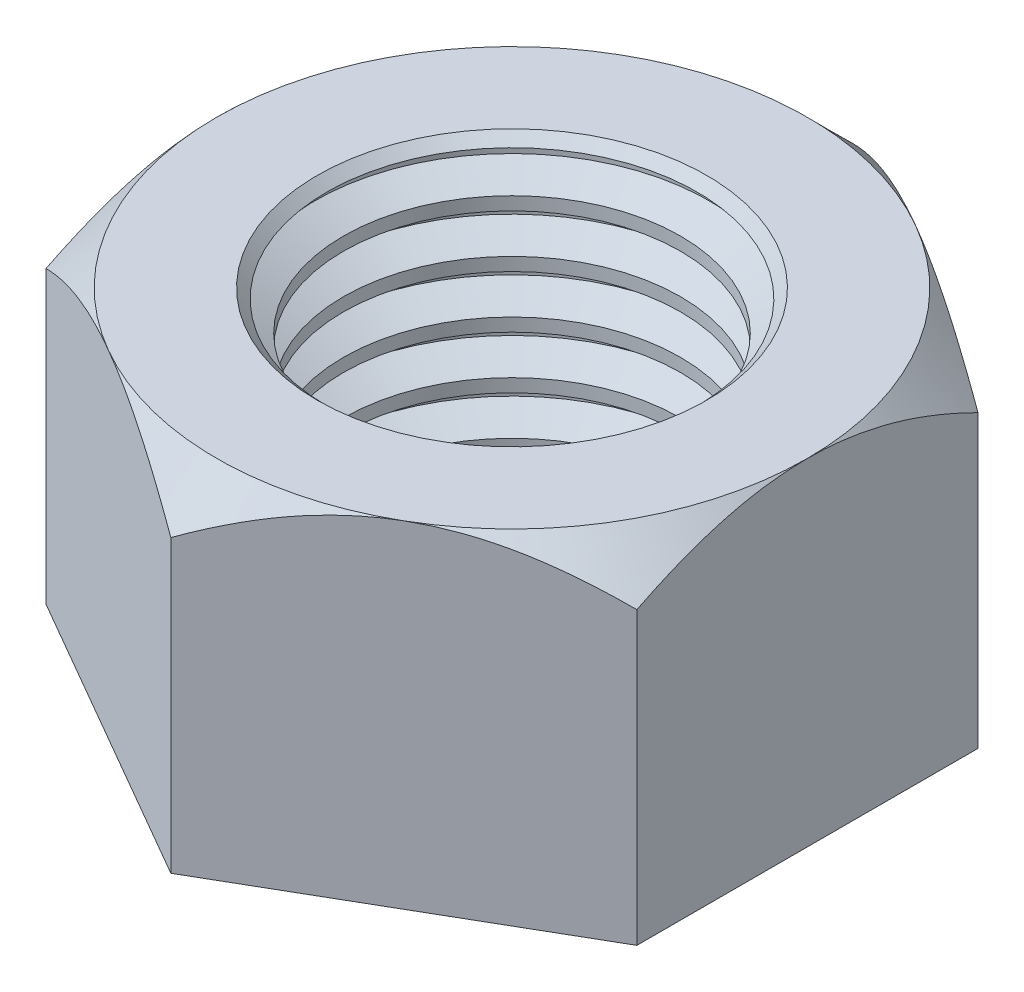
SolidWorks part; units mm, degrees
ref_plane "Front" through (0, 0, 0) normal (0, 0, 1) x (1, 0, 0)
ref_plane "Top" through (0, 0, 0) normal (0, 1, 0) x (1, 0, 0)
ref_plane "Right" through (0, 0, 0) normal (1, 0, 0) x (0, 0, -1)
sketch "Sketch1" plane through (0, 0, 0) normal (0, 1, 0) x (1, 0, 0)
  line L1 (0, 16.4978) -> (-14.2875, 8.2489)
  line L2 (-14.2875, 8.2489) -> (-14.2875, -8.2489)
  line L3 (-14.2875, -8.2489) -> (0, -16.4978)
  line L4 (0, -16.4978) -> (14.2875, -8.2489)
  line L5 (14.2875, -8.2489) -> (14.2875, 8.2489)
  line L6 (14.2875, 8.2489) -> (0, 16.4978)
  circle A0 centre (0, 0) radius 14.2875 construction
  dimension "Hex Flats" = 28.575
extrude "Extrude1" add sketch "Sketch1" along normal blind 16.2719
sketch "Sketch3" plane through (0, 0, 0) normal (1, 0, 0) x (0, 0, -1)
  line L0 (14.2875, 16.2719) -> (16.4978, 14.0616)
  line L1 (8.2489, 16.2719) -> (16.4978, 16.2719) construction
  line L2 (16.4978, 16.2719) -> (16.4978, 0) construction
  line L3 (16.4978, 14.0616) -> (16.4978, 16.2719)
  line L4 (16.4978, 16.2719) -> (14.2875, 16.2719)
  line L5 (0, 0.542) -> (0, -0.542) construction
  dimension "D1" = 45
  dimension "D2" = 28.575
revolve "Cut-Revolve2" cut sketch "Sketch3" angle 360 about L5
sketch "Sketch2" plane through (0, 0, 0) normal (0, 0, 1) x (1, 0, 0)
  line L0 (0, 1.6636) -> (0, -0.3796) construction
  line L1 (0, 16.2719) -> (8.1502, 16.2719)
  line L3 (0, 16.2719) -> (14.2875, 16.2719) construction
  line L4 (0, 13.7319) -> (8.1502, 13.7319)
  line L5 (8.1502, 16.2719) -> (9.525, 15.4781)
  line L6 (9.525, 15.4781) -> (9.525, 15.1606)
  line L7 (9.525, 15.1606) -> (8.1502, 14.3669)
  line L9 (8.1502, 13.7319) -> (8.1502, 14.3669)
  line L10 (0, 13.7319) -> (0, 16.2719)
  line L11 (8.1502, 16.2719) -> (8.1502, 14.3669) construction
  line L12 (9.525, 15.3194) -> (8.1502, 15.3194) construction
  dimension "D1" = 60
  dimension "D2" = 0.635
  dimension "D5" = 0.3175
  dimension "Pitch" = 2.54
  dimension "Major Dia." = 19.05
revolve "Cut-Revolve1" cut sketch "Sketch2" angle 360 about L0
pattern_linear "LPattern2" count 7 spacing 2.54 along (0, -1, 0) of "Cut-Revolve1"
chamfer "Chamfer1" distance 1.27 angle 45 1 edges at (0, 16.2719, 8.1502) first distance on face at (0, 16.2719, 0)
equation "\"D5@Sketch2\"=\"Pitch@Sketch2\"/8"
equation "\"D2@Sketch2\"=\"Pitch@Sketch2\"/4"
equation "\"D3@LPattern2\"=\"Pitch@Sketch2\""
equation "\"D1@LPattern2\"=int(\"Height@Extrude1\"/\"Pitch@Sketch2\")+1"
equation "\"D2@Sketch3\"=\"Hex Flats@Sketch1\""
equation "\"D1@Chamfer1\"=\"Pitch@Sketch2\"/2"
